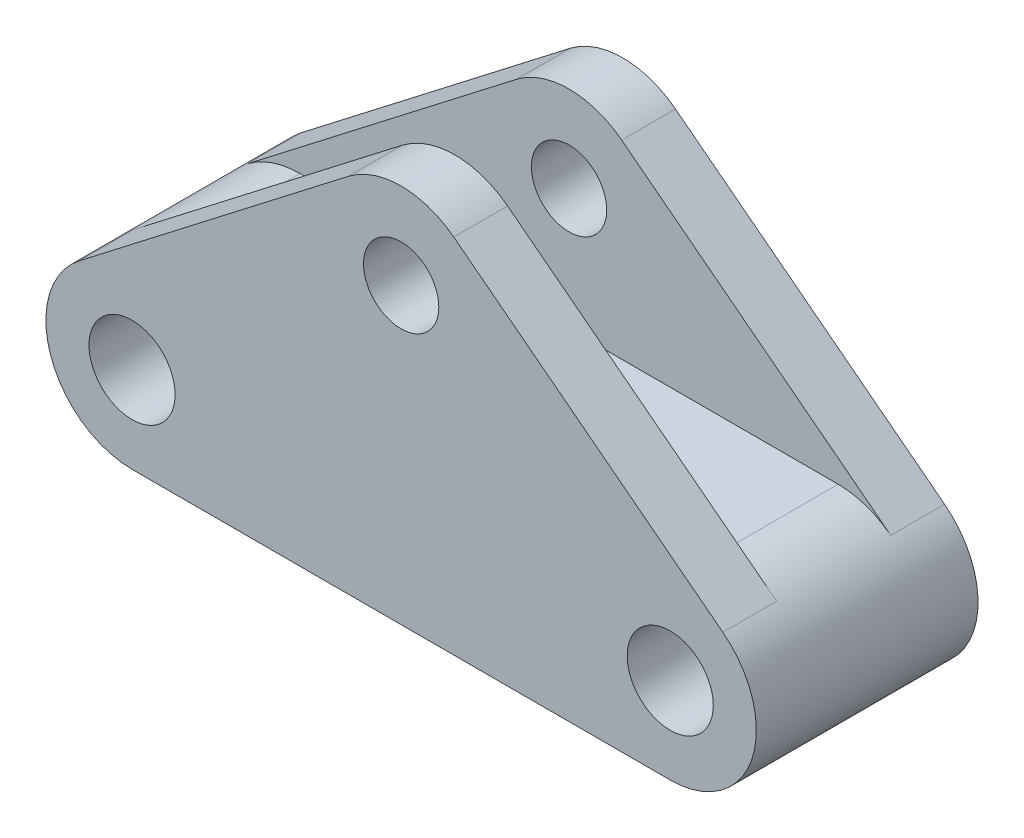
SolidWorks part; units mm, degrees
material "ABS"
ref_plane "Front Plane" through (0, 0, 0) normal (0, 0, 1) x (1, 0, 0)
ref_plane "Top Plane" through (0, 0, 0) normal (0, 1, 0) x (1, 0, 0)
ref_plane "Right Plane" through (0, 0, 0) normal (1, 0, 0) x (0, 0, -1)
sketch "Sketch1" plane through (0, 0, 0) normal (0, 0, 1) x (1, 0, 0)
  line L0 (0, 27.2364) -> (0, -32.7408) construction
  line L1 (25, -27.3) -> (-25, -27.3)
  line L2 (-29.8887, -12.9675) -> (-4.8887, 6.3325)
  line L3 (29.8887, -12.9675) -> (4.8887, 6.3325)
  line L4 (-25, -11.3) -> (25, -11.3)
  circle A0 centre (0, 0) radius 3.5
  circle A1 centre (0, 0) radius 11
  circle A2 centre (-25, -19.3) radius 4
  arc A3 (-25, -27.3) -> (-29.8887, -12.9675) centre (-25, -19.3) cw
  arc A4 (-4.8887, 6.3325) -> (4.8887, 6.3325) centre (0, 0) cw
  arc A5 (25, -27.3) -> (29.8887, -12.9675) centre (25, -19.3) ccw
  circle A6 centre (25, -19.3) radius 4
  arc A7 (-25, -11.3) -> (-29.8887, -12.9675) centre (-25, -19.3) ccw
  arc A8 (25, -11.3) -> (29.8887, -12.9675) centre (25, -19.3) cw
  point P8 (0, 11)
  point P15 (0, -27.3)
  point P21 (0, -11.3)
  dimension "D1" = 7
  dimension "D2" = 22
  dimension "D3" = 8
  dimension "D6" = 8
  dimension "D7" = 8
  dimension "D4" = 25
  dimension "D5" = 30.3
extrude "Boss-Extrude1" add sketch "Sketch1" against normal blind 5 contours L0 L4 A7 A3 L1 A2 | L4 L0 L1 A5 A8 A6 | A1 L0 L4 A8 L3 | A4 L0 A0 A1 L3 | L0 A4 L2 A1 A0 | L0 A1 L2 A7 L4 region at (4.9704, -1.8523, 0) region at (-4.9704, -1.8523, 0) region at (14.8622, -7.4078, 0) region at (-14.8622, -7.4078, 0) region at (14.6535, -19.3, 0) region at (-14.6535, -19.3, 0)
extrude "Boss-Extrude2" add sketch "Sketch1<3>" against normal blind 10.6 from vertex contours L0 L4 A7 A3 L1 A2 | L4 L0 L1 A5 A8 A6 region at (14.6535, -19.3, 0) region at (-14.6535, -19.3, 0) starting at point (-29.8887, -12.9675, -5)
sketch "Sketch1<3>" plane through (0, 0, 0) normal (0, 0, 1) x (1, 0, 0) same geometry as "Sketch1"
extrude "Boss-Extrude3" add sketch "Sketch1<4>" against normal blind 5 from vertex contours L0 A1 L2 A7 L4 | L0 A4 L2 A1 A0 | A4 L0 A0 A1 L3 | A1 L0 L4 A8 L3 | L4 L0 L1 A5 A8 A6 | L0 L4 A7 A3 L1 A2 region at (4.9704, -1.8523, 0) region at (-4.9704, -1.8523, 0) region at (14.8622, -7.4078, 0) region at (-14.8622, -7.4078, 0) region at (14.6535, -19.3, 0) region at (-14.6535, -19.3, 0) starting at point (-25, -27.3, -15.6)
sketch "Sketch1<4>" plane through (0, 0, 0) normal (0, 0, 1) x (1, 0, 0) same geometry as "Sketch1"
equation "\"rod_diameter\"= 8"
equation "\"rod_hole_thickness\"= 4"
equation "\"rod_radius\"= \"rod_diameter\" / 2"
equation "\"platter_diameter\"= 320"
equation "\"platter_radius\"= \"platter_diameter\" / 2"
equation "\"extruder_mount_hole_spacing\"= 75"
equation "\"arm_rod_spacing\"= 40"
equation "\"top_frame_rod_spacing\"= \"arm_rod_spacing\" + 40"
equation "\"motor_level_rod_spacing\"= 15"
equation "\"linear_bearing_diameter\"= 15"
equation "\"z_rod_spacing\"= 75"
equation "\"platter_rod_spacing\"= 50"
equation "\"rod_nut_thickness\"= 6.5"
equation "\"rod_nut_inscribed_diameter\"= 13"
equation "\"z_height\"= 400"
equation "\"D1@Sketch1\"=\"rod_diameter\"-1"
equation "\"D3@Sketch1\"=\"rod_diameter\""
equation "\"D4@Sketch1\"=\"platter_rod_spacing\"/2"
equation "\"D6@Sketch1\"=\"rod_radius\"+\"rod_hole_thickness\""
equation "\"D7@Sketch1\"=\"rod_radius\"+\"rod_hole_thickness\""
